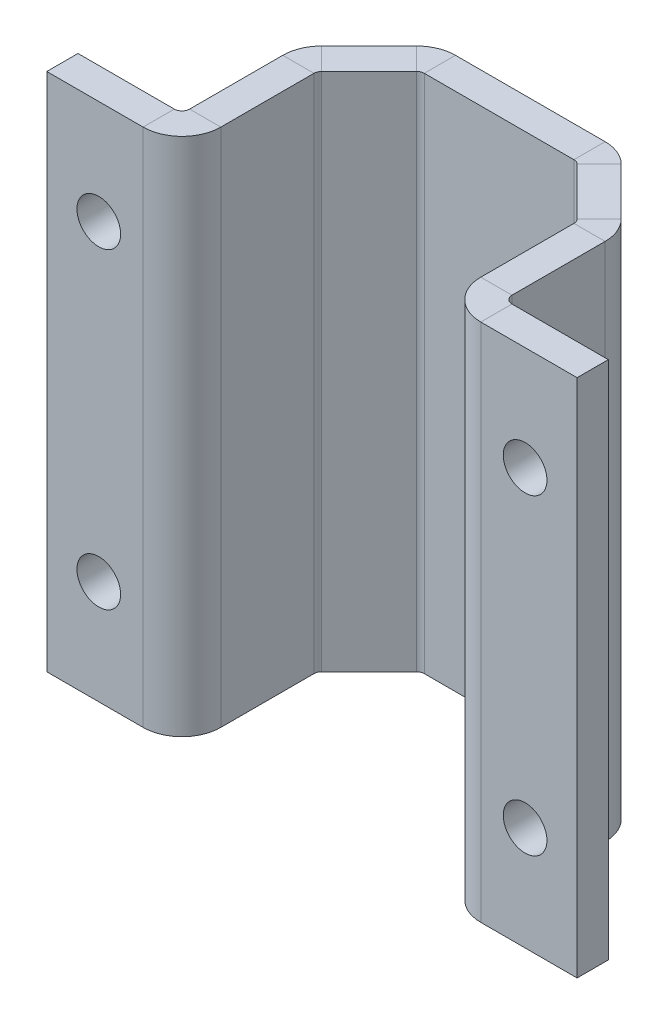
SolidWorks part; units mm, degrees
note: The reader was unsure of these and kept them because the rebuilt part matched: flange length of "Edge-Flange5", "Edge-Flange6", "Edge-Flange7".
ref_plane "Front Plane" through (0, 0, 0) normal (0, 0, 1) x (1, 0, 0)
ref_plane "Top Plane" through (0, 0, 0) normal (0, 1, 0) x (1, 0, 0)
ref_plane "Right Plane" through (0, 0, 0) normal (1, 0, 0) x (0, 0, -1)
sketch "Sketch1" plane through (0, 0, 0) normal (0, 0, 1) x (1, 0, 0)
  line L1 (0, 0) -> (15, 0)
  line L2 (0, 0) -> (0, 50)
  line L3 (0, 50) -> (15, 50)
  line L4 (15, 0) -> (15, 50)
  dimension "D1" = 50
  dimension "D2" = 15
base flange "Base-Flange1" sketch "Sketch1" thickness 3 reverse thickness direction no parameters "D1"=0.7366
edge flange "Edge-Flange5" sketch "Sketch33" flange profiles "Sketch33", "Sketch34" flange angle 135 flange length 7.071 flange position material outside bend radius 0.7366 thickness 3 relief rectangular parameters "D6"=10, "D8"=1
sketch "Sketch33" plane through (15, 0, 0) normal (0.7071, 0, -0.7071) x (0, 1, 0)
  line L2 (0, 0) -> (0, 7.071)
  line L3 (0, 7.071) -> (50, 7.071)
  line L4 (50, 7.071) -> (50, 0)
  line L11 (0, 0) -> (50, 0) construction
  line L12 (0, 0) -> (50, 0)
sketch "Sketch34" plane through (0, 0, 0) normal (-0.7071, 0, -0.7071) x (0, -1, 0)
  line L2 (-50, 0) -> (-50, 7.071)
  line L3 (-50, 7.071) -> (0, 7.071)
  line L4 (0, 7.071) -> (0, 0)
  line L11 (-50, 0) -> (0, 0) construction
  line L12 (-50, 0) -> (0, 0)
bend "EdgeBend7" bend radius 0.7366 bend angle 45 parameters "D5"=1
bend "EdgeBend8" bend radius 0.7366 bend angle 45 parameters "D5"=2
edge flange "Edge-Flange6" sketch "Sketch39" flange profiles "Sketch39", "Sketch40" flange angle 135 flange length 10 flange position material outside bend radius 0.7366 thickness 3 relief rectangular parameters "D6"=10, "D8"=1
sketch "Sketch39" plane through (-5, 0, 5) normal (-1, 0, 0) x (0, -1, 0)
  line L2 (-50, 0) -> (-50, 10)
  line L3 (-50, 10) -> (0, 10)
  line L4 (0, 10) -> (0, 0)
  line L23 (0, 0) -> (-50, 0) construction
  line L24 (0, 0) -> (-50, 0)
sketch "Sketch40" plane through (20, 0, 5) normal (1, 0, 0) x (0, 1, 0)
  line L2 (50, 0) -> (50, 10)
  line L3 (50, 10) -> (0, 10)
  line L4 (0, 10) -> (0, 0)
  line L9 (50, 0) -> (0, 0) construction
  line L10 (50, 0) -> (0, 0)
bend "EdgeBend9" bend radius 0.7366 bend angle 45 parameters "D5"=3
bend "EdgeBend10" bend radius 0.7366 bend angle 45 parameters "D5"=4
edge flange "Edge-Flange7" sketch "Sketch45" flange profiles "Sketch45", "Sketch46" flange angle 90 flange length 10 flange position material outside bend radius 0.7366 thickness 3 relief rectangular parameters "D6"=10, "D8"=1
sketch "Sketch45" plane through (-8, 0, 15) normal (0, 0, 1) x (0, 1, 0)
  line L2 (0, 0) -> (0, 10)
  line L3 (0, 10) -> (50, 10)
  line L4 (50, 10) -> (50, 0)
  line L7 (0, 0) -> (50, 0) construction
  line L8 (0, 0) -> (50, 0)
sketch "Sketch46" plane through (23, 0, 15) normal (0, 0, 1) x (0, -1, 0)
  line L2 (-50, 0) -> (-50, 10)
  line L3 (-50, 10) -> (0, 10)
  line L4 (0, 10) -> (0, 0)
  line L7 (-50, 0) -> (0, 0) construction
  line L8 (-50, 0) -> (0, 0)
bend "EdgeBend11" bend radius 0.7366 bend angle 90 parameters "D5"=5
bend "EdgeBend12" bend radius 0.7366 bend angle 90 parameters "D5"=6
sketch "Sketch49" plane through (0, 0, 18) normal (0, 0, 1) x (1, 0, 0)
  line L0 (-18, 50) -> (-18, 0) construction
  line L1 (-8.7366, 50) -> (-18, 50) construction
  line L2 (33, 0) -> (33, 50) construction
  point P0 (-13, 10)
  point P2 (-13, 40)
  point P4 (28, 10)
  point P6 (28, 40)
  point P9 (0, 0)
  point P10 (0, 0)
  point P11 (0, 0)
  point P12 (0, 0)
  point P13 (0, 0)
  dimension "D1" = 5
  dimension "D2" = 30
  dimension "D3" = 10
  dimension "D4" = 5
hole_wizard "Tap Drill for M5x0.8 Tap1" positions "Sketch49" profile "Sketch48" hole size "M5x0.8" standard "ANSI Metric" end condition through all
sketch "Sketch48" plane through (-13, 10, 18) normal (1, 0, 0) x (0, -1, 0)
  line L0 (0, 0) -> (0, 21)
  line L1 (0, 21) -> (2.1, 21)
  line L2 (2.1, 21) -> (2.1, 0)
  line L5 (2.1, 0) -> (0, 0)
  line L11 (0, -6.35) -> (0, 107.95) construction
  dimension "Thru Hole Dia." = 4.2
  dimension "Thru Hole Depth" = 21
sketch "Bend-Lines1" [suppressed] plane through (0, 0, 0) normal (0, 1, 0) x (1, 0, 0)
sketch "Bounding-Box1" [suppressed] plane through (0, 0, 0) normal (0, 1, 0) x (1, 0, 0)
sheet metal parameters "Sheet-Metal11" thickness 3 parameters "D1"=0.7366
flat pattern "Flat-Pattern11" [suppressed]
sketch "Bend-Lines2" plane through (0, 0, 0) normal (0, 1, 0) x (1, 0, 0)
sketch3d "Bounding-Box2" [suppressed]
  line L0 (-15, 50, 0) -> (-15, 0, 0) construction
  line L1 (0, 50, 0) -> (0, 0, 0) construction
  line L2 (-15, 50, 0) -> (0, 50, 0) construction
  line L3 (-15, 0, 0) -> (0, 0, 0) construction
sheet metal parameters "Sheet-Metal12" thickness 3 parameters "D1"=0.7366
flat pattern "Flat-Pattern11"
sketch "Bend-Lines2" plane through (0, 0, 0) normal (0, 0, 1) x (1, 0, 0)
  line L0 (-0.5732, 50) -> (-0.5732, 0) construction
  line L1 (15.5732, 0) -> (15.5732, 50) construction
  line L2 (-0.5732, 50) -> (-0.5732, 0) construction
  line L3 (15.5732, 0) -> (15.5732, 50) construction
sketch3d "Bounding-Box2" [suppressed]
  line L0 (23.2174, 50, 0) -> (23.2174, 0, 0) construction
  line L1 (-8.2174, 50, 0) -> (-8.2174, 0, 0) construction
  line L2 (23.2174, 50, 0) -> (-8.2174, 50, 0) construction
  line L3 (23.2174, 0, 0) -> (-8.2174, 0, 0) construction
bend of the flat pattern "Flatten-<EdgeBend7>1"
bend of the flat pattern "Flatten-<EdgeBend8>1"
sheet metal parameters "Sheet-Metal13" thickness 3 parameters "D1"=0.7366
flat pattern "Flat-Pattern11"
sketch "Bend-Lines2" plane through (0, 0, 0) normal (0, 0, 1) x (1, 0, 0)
  line L0 (-0.5732, 50) -> (-0.5732, 0) construction
  line L1 (15.5732, 0) -> (15.5732, 50) construction
  line L2 (-0.5732, 50) -> (-0.5732, 0) construction
  line L3 (15.5732, 0) -> (15.5732, 50) construction
  line L4 (23.7906, 0) -> (23.7906, 50) construction
  line L5 (-8.7906, 50) -> (-8.7906, 0) construction
  line L6 (23.7906, 0) -> (23.7906, 50) construction
  line L7 (-8.7906, 50) -> (-8.7906, 0) construction
sketch3d "Bounding-Box2" [suppressed]
  line L0 (-19.3638, 0, 0) -> (34.3638, 0, 0) construction
  line L1 (-19.3638, 50, 0) -> (34.3638, 50, 0) construction
  line L2 (-19.3638, 0, 0) -> (-19.3638, 50, 0) construction
  line L3 (34.3638, 0, 0) -> (34.3638, 50, 0) construction
bend of the flat pattern "Flatten-<EdgeBend7>1"
bend of the flat pattern "Flatten-<EdgeBend8>1"
bend of the flat pattern "Flatten-<EdgeBend9>1"
bend of the flat pattern "Flatten-<EdgeBend10>1"
sheet metal parameters "Sheet-Metal14" thickness 3 parameters "D1"=0.7366
flat pattern "Flat-Pattern11"
sketch "Bend-Lines2" plane through (0, 0, 0) normal (0, 0, 1) x (1, 0, 0)
  line L0 (-0.5732, 50) -> (-0.5732, 0) construction
  line L1 (15.5732, 0) -> (15.5732, 50) construction
  line L2 (-0.5732, 50) -> (-0.5732, 0) construction
  line L3 (15.5732, 0) -> (15.5732, 50) construction
  line L4 (23.7906, 0) -> (23.7906, 50) construction
  line L5 (-8.7906, 50) -> (-8.7906, 0) construction
  line L6 (23.7906, 0) -> (23.7906, 50) construction
  line L7 (-8.7906, 50) -> (-8.7906, 0) construction
  line L8 (35.3838, 0) -> (35.3838, 50) construction
  line L9 (-20.3838, 50) -> (-20.3838, 0) construction
  line L10 (35.3838, 0) -> (35.3838, 50) construction
  line L11 (-20.3838, 50) -> (-20.3838, 0) construction
sketch3d "Bounding-Box2" [suppressed]
  line L0 (-31.4038, 0, 0) -> (46.4038, 0, 0) construction
  line L1 (-31.4038, 50, 0) -> (46.4038, 50, 0) construction
  line L2 (-31.4038, 0, 0) -> (-31.4038, 50, 0) construction
  line L3 (46.4038, 0, 0) -> (46.4038, 50, 0) construction
bend of the flat pattern "Flatten-<EdgeBend7>1"
bend of the flat pattern "Flatten-<EdgeBend8>1"
bend of the flat pattern "Flatten-<EdgeBend9>1"
bend of the flat pattern "Flatten-<EdgeBend10>1"
bend of the flat pattern "Flatten-<EdgeBend11>1"
bend of the flat pattern "Flatten-<EdgeBend12>1"
sheet metal parameters "Sheet-Metal15" thickness 3 parameters "D1"=0.7366
flat pattern "Flat-Pattern11"
sketch "Bend-Lines2" plane through (0, 0, 0) normal (0, 0, 1) x (1, 0, 0)
  line L0 (-0.5732, 50) -> (-0.5732, 0) construction
  line L1 (15.5732, 0) -> (15.5732, 50) construction
  line L2 (-0.5732, 50) -> (-0.5732, 0) construction
  line L3 (15.5732, 0) -> (15.5732, 50) construction
  line L4 (23.7906, 0) -> (23.7906, 50) construction
  line L5 (-8.7906, 50) -> (-8.7906, 0) construction
  line L6 (23.7906, 0) -> (23.7906, 50) construction
  line L7 (-8.7906, 50) -> (-8.7906, 0) construction
  line L8 (35.3838, 0) -> (35.3838, 50) construction
  line L9 (-20.3838, 50) -> (-20.3838, 0) construction
  line L10 (35.3838, 0) -> (35.3838, 50) construction
  line L11 (-20.3838, 50) -> (-20.3838, 0) construction
sketch3d "Bounding-Box2" [suppressed]
  line L0 (-31.4038, 0, 0) -> (46.4038, 0, 0) construction
  line L1 (-31.4038, 50, 0) -> (46.4038, 50, 0) construction
  line L2 (-31.4038, 0, 0) -> (-31.4038, 50, 0) construction
  line L3 (46.4038, 0, 0) -> (46.4038, 50, 0) construction
bend of the flat pattern "Flatten-<EdgeBend7>1"
bend of the flat pattern "Flatten-<EdgeBend8>1"
bend of the flat pattern "Flatten-<EdgeBend9>1"
bend of the flat pattern "Flatten-<EdgeBend10>1"
bend of the flat pattern "Flatten-<EdgeBend11>1"
bend of the flat pattern "Flatten-<EdgeBend12>1"
